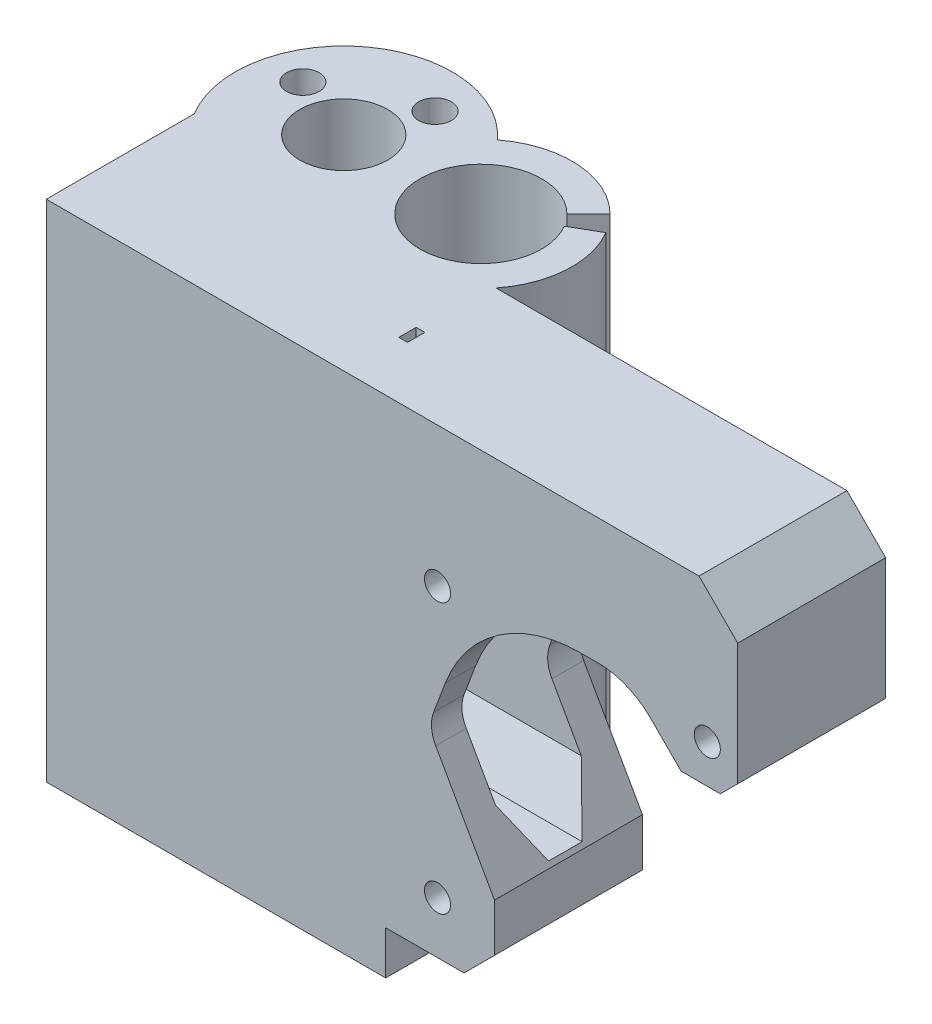
SolidWorks part; units mm, degrees
ref_plane "Front Plane" through (0, 0, 0) normal (0, 0, 1) x (1, 0, 0)
ref_plane "Top Plane" through (0, 0, 0) normal (0, 1, 0) x (1, 0, 0)
ref_plane "Right Plane" through (0, 0, 0) normal (1, 0, 0) x (0, 0, -1)
sketch "Sketch1" plane through (0, 0, 0) normal (0, 0, 1) x (1, 0, 0)
  line L0 (39, -53) -> (48, -53)
  line L1 (0, 0) -> (39, 0)
  line L2 (0, 0) -> (0, -58)
  line L3 (0, -58) -> (39, -58)
  line L4 (39, -53) -> (39, -58)
  line L5 (39, 0) -> (75, 0)
  line L6 (75, 0) -> (79.45, -4.45)
  line L7 (79.45, -4.45) -> (79.45, -18.45)
  line L8 (79.45, -18.45) -> (77.45, -20.45)
  line L9 (77.45, -20.45) -> (72.95, -20.45)
  line L10 (72.95, -20.45) -> (69.45, -16.95)
  line L12 (45.8405, -25.2376) -> (44.5009, -28.8048)
  line L13 (44.75, -32.0294) -> (51.5, -44)
  line L14 (51.5, -44) -> (51.5, -49.5)
  line L15 (61.4145, -14.45) -> (63.4145, -14.45)
  line L16 (51.5, -49.5) -> (48, -53)
  arc A5 (63.4145, -14.45) -> (69.45, -16.95) centre (63.4145, -22.9855) cw
  arc A6 (61.4145, -14.45) -> (45.8405, -25.2376) centre (61.4145, -31.0859) ccw
  arc A7 (44.5009, -28.8048) -> (44.75, -32.0294) centre (48.083, -30.15) ccw
  dimension "D1" = 58
  dimension "D2" = 39
  dimension "D3" = 75
  dimension "D4" = 4.45
  dimension "D5" = 135
  dimension "D6" = 14
  dimension "D7" = 2
  dimension "D8" = 3.5
  dimension "D9" = 6
  dimension "D10" = 5
  dimension "D11" = 4.5
  dimension "D12" = 130
  dimension "D13" = 3.5
  dimension "D14" = 5.5
  dimension "D15" = 6.75
  dimension "D16" = 9
  dimension "D17" = 13.85
  dimension "D18" = 3.417
  dimension "D19" = 2
extrude "Boss-Extrude1" add sketch "Sketch1" along normal blind 17
sketch "Sketch2" plane through (0, 0, 0) normal (0, 1, 0) x (1, 0, 0)
  line L0 (0, -17) -> (0, 6.5) construction
  line L1 (0, 6.5) -> (26.427, 6.5) construction
  circle A0 centre (26.427, 6.5) radius 10.5
  dimension "D2" = 21
  dimension "D1" = 23.5
  dimension "D3" = 26.427
extrude "Boss-Extrude2" add sketch "Sketch2" against normal up to surface (58 mm away) up to face at (19.5, -58, 8.5)
sketch "Sketch3" plane through (0, 0, 0) normal (0, 1, 0) x (1, 0, 0)
  line L0 (0, -17) -> (0, 20.4292) construction
  line L1 (10.6771, 6.5) -> (0, 6.5) construction
  line L2 (75, -17) -> (0, -17) construction
  circle A0 centre (10.6771, 6.5) radius 12.5
  dimension "D3" = 25
  dimension "D2" = 23.5
extrude "Boss-Extrude3" add sketch "Sketch3" against normal blind 13.5
sketch "Sketch4" plane through (0, 0, 0) normal (0, 1, 0) x (1, 0, 0)
  circle A0 centre (26.427, 6.5) radius 7
  circle A1 centre (10.6771, 6.5) radius 5.05
  dimension "D1" = 10.1
  dimension "D2" = 14
extrude "Cut-Extrude1" cut sketch "Sketch4" against normal through all
sketch "Sketch5" plane through (0, 0, 0) normal (-1, 0, 0) x (0, 0, 1)
  line L0 (10.5, -43.5) -> (6.65, -43.5)
  line L1 (6.65, -43.5) -> (3.65, -38)
  line L2 (3.65, -38) -> (3.65, -19)
  line L3 (3.65, -19) -> (6.65, -16)
  line L4 (6.65, -16) -> (10.5, -16)
  line L5 (10.5, -16) -> (13.5, -19)
  line L6 (13.5, -19) -> (13.5, -38)
  line L7 (13.5, -38) -> (10.5, -43.5)
  line L8 (17, 0) -> (0, 0) construction
  line L9 (17, 0) -> (17, -58) construction
  circle A0 centre (8.5, -6) radius 4.05
  circle A1 centre (8.5, -51) radius 4.05
  dimension "D8" = 8.1
  dimension "D9" = 8.1
  dimension "D1" = 19
  dimension "D2" = 3
  dimension "D3" = 3.85
  dimension "D4" = 16
  dimension "D5" = 6
  dimension "D6" = 51
  dimension "D7" = 5.5
  dimension "D10" = 3
  dimension "D11" = 3
  dimension "D12" = 19
  dimension "D13" = 3.85
  dimension "D14" = 3
  dimension "D15" = 3
  dimension "D16" = 3.5
  dimension "D17" = 8.5
  dimension "D18" = 8.5
extrude "Cut-Extrude2" cut sketch "Sketch5" against normal blind 35
sketch "Sketch6" plane through (0, 0, 0) normal (0, 0, -1) x (-1, 0, 0)
  line L0 (-75.9503, -16.0252) -> (-44.9503, -16.0252) construction
  line L1 (-44.9503, -16.0252) -> (-44.9503, -47.0252) construction
  line L2 (-44.9503, -47.0252) -> (-75.9503, -47.0252) construction
  line L3 (-75.9503, -47.0252) -> (-75.9503, -16.0252) construction
  line L4 (-75.9503, -31.5252) -> (-44.9503, -31.5252) construction
  line L5 (-60.4503, -16.0252) -> (-60.4503, -47.0252) construction
  circle A0 centre (-75.9503, -16.0252) radius 1.5
  circle A1 centre (-44.9503, -16.0252) radius 1.5
  circle A2 centre (-44.9503, -47.0252) radius 1.5
  circle A3 centre (-60.4503, -31.5252) radius 11 construction
  point P14 (-60.4503, -31.5252)
  dimension "D3" = 22
  dimension "D4" = 3
  dimension "D1" = 31
  dimension "D2" = 31
extrude "Cut-Extrude3" cut sketch "Sketch6" against normal through all
sketch "Sketch8" plane through (35, 0, 0) normal (-1, 0, 0) x (0, 0, 1)
  line L8 (10.5, -43.5) -> (13.5, -38)
  line L9 (13.5, -38) -> (13.5, -19)
  line L10 (13.5, -19) -> (10.5, -16)
  line L11 (10.5, -16) -> (6.65, -16)
  line L12 (6.65, -16) -> (3.65, -19)
  line L13 (3.65, -19) -> (3.65, -38)
  line L14 (3.65, -38) -> (6.65, -43.5)
  line L15 (6.65, -43.5) -> (10.5, -43.5)
  line L16 (10.5, -43.5) -> (13.5, -38)
  line L17 (13.5, -38) -> (13.5, -19)
  line L18 (13.5, -19) -> (10.5, -16)
  line L19 (10.5, -16) -> (6.65, -16)
  line L20 (6.65, -16) -> (3.65, -19)
  line L21 (3.65, -19) -> (3.65, -38)
  line L22 (3.65, -38) -> (6.65, -43.5)
  line L23 (6.65, -43.5) -> (10.5, -43.5)
  dimension "D1" = 0
extrude "Cut-Extrude4" cut sketch "Sketch8" against normal blind 20
sketch "Sketch9" plane through (0, 0, 0) normal (0, 1, 0) x (1, 0, 0)
  line L0 (32.4461, 10.0735) -> (35.4774, 11.8236)
  line L1 (31.3767, 11.4497) -> (33.8516, 13.9246)
  line L2 (26.427, 6.5) -> (36.927, 6.5) construction
  line L3 (32.4461, 10.0735) -> (26.427, 6.5) construction
  line L4 (26.427, 6.5) -> (31.3767, 11.4497) construction
  arc A0 (32.4461, 10.0735) -> (31.3767, 11.4497) centre (26.427, 6.5) ccw
  arc A1 (35.4774, 11.8236) -> (33.8516, 13.9246) centre (26.427, 6.5) ccw
  arc A2 (34.6732, 0) -> (20.0124, 14.8128) centre (26.427, 6.5) ccw construction
  circle A3 centre (26.427, 6.5) radius 7 construction
  dimension "D1" = 15
  dimension "D2" = 30
extrude "Cut-Extrude5" cut sketch "Sketch9" against normal through all
sketch "Sketch10" plane through (0, 0, 0) normal (0, 1, 0) x (1, 0, 0)
  line L0 (13.5702, 14.0925) -> (10.6771, 6.5) construction
  line L1 (10.6771, 6.5) -> (3.0846, 9.3931) construction
  circle A0 centre (13.5702, 14.0925) radius 1.875
  circle A1 centre (3.0846, 9.3931) radius 1.875
  dimension "D3" = 3.75
  dimension "D4" = 3.75
  dimension "D1" = 90
  dimension "D2" = 8.125
  dimension "D5" = 8.125
extrude "Cut-Extrude6" cut sketch "Sketch10" against normal through all
sketch "Sketch11" plane through (0, -58, 0) normal (0, -1, 0) x (1, 0, 0)
  line L0 (0, 17) -> (0, 0) construction
  line L1 (35, 8.5) -> (34, 8.5)
  line L2 (35, 8.5) -> (35, 10.5)
  line L3 (35, 10.5) -> (34, 10.5)
  line L4 (34, 8.5) -> (34, 10.5)
  line L5 (0, 17) -> (39, 17) construction
  dimension "D1" = 35
  dimension "D2" = 1
  dimension "D3" = 2
  dimension "D4" = 6.5
extrude "Cut-Extrude7" cut sketch "Sketch11" against normal blind 8
ref_plane "Plane1" through (0, -29, 0) normal (0, 1, 0) x (1, 0, 0)
mirror "Mirror1" about plane through (0, -29, 0) normal (0, 1, 0) of "Cut-Extrude7"
